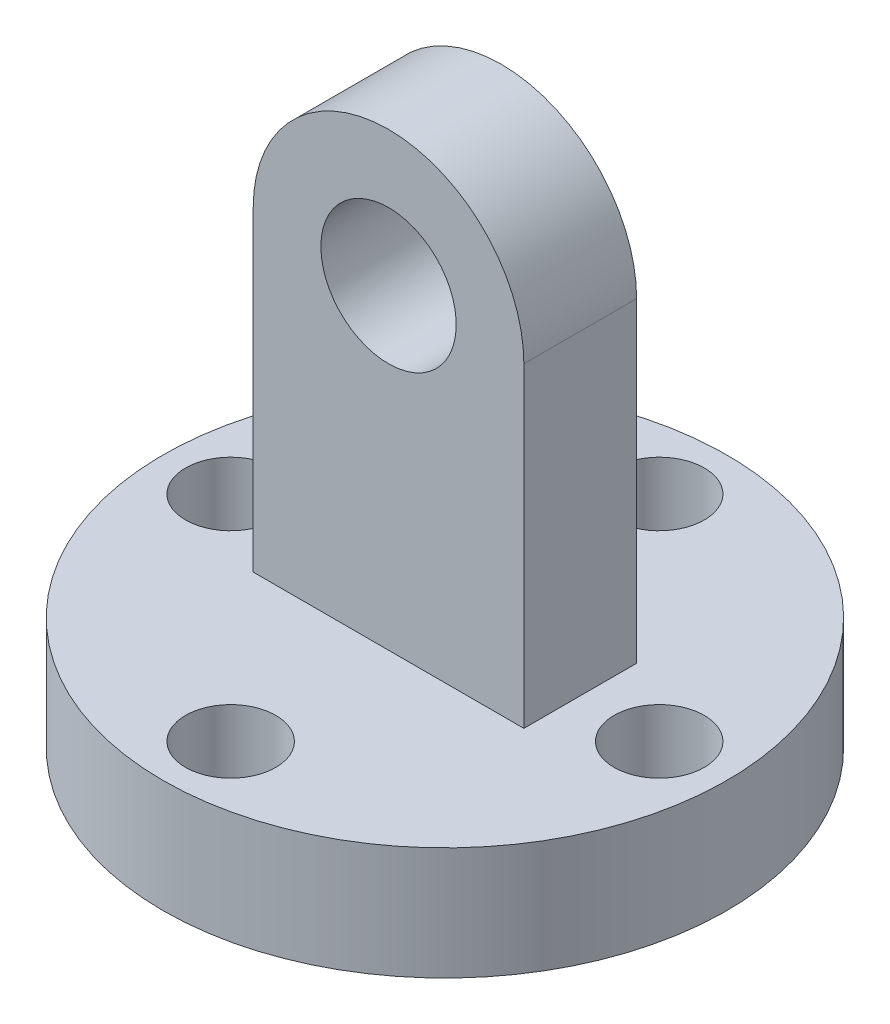
SolidWorks part; units mm, degrees
ref_plane "前视基准面" through (0, 0, 0) normal (0, 0, 1) x (1, 0, 0)
ref_plane "上视基准面" through (0, 0, 0) normal (0, 1, 0) x (1, 0, 0)
ref_plane "右视基准面" through (0, 0, 0) normal (1, 0, 0) x (0, 0, -1)
other "Configuration Table"
sketch "草图1" plane through (0, 0, 0) normal (0, 1, 0) x (1, 0, 0)
  circle A7 centre (0, 0) radius 12.5
  point P0 (0, 0)
  dimension "D4" = 25
extrude "凸台-拉伸1" add sketch "草图1" along normal blind 5
sketch "草图2" plane through (0, 5, 0) normal (0, 1, 0) x (1, 0, 0)
  line L0 (0, -9.5) -> (0, 9.5) construction
  line L1 (9.5, 0) -> (-9.5, 0) construction
  circle A0 centre (0, -9.5) radius 1.1
  circle A1 centre (0, 9.5) radius 1.1
  circle A2 centre (9.5, 0) radius 1.1
  circle A3 centre (-9.5, 0) radius 1.1
  circle A5 centre (-9.5, 0) radius 2
  circle A6 centre (0, 9.5) radius 2
  circle A7 centre (9.5, 0) radius 2
  circle A8 centre (0, -9.5) radius 2
  dimension "D1" = 2.2
  dimension "D3" = 4
  dimension "D2" = 19
extrude "切除-拉伸1" cut sketch "草图2" against normal through all contours A3 | A1 | A2 | A0
extrude "切除-拉伸2" cut sketch "草图2<3>" against normal offset from surface (3 mm away) 2 contours A5 | A6 | A8 | A7 up to face at (-9.5, 0, 1.1)
sketch "草图2<3>" plane through (0, 5, 0) normal (0, 1, 0) x (1, 0, 0) same geometry as "草图2"
sketch "草图3" plane through (0, 5, 0) normal (0, 1, 0) x (1, 0, 0)
  line L1 (6, 2.5) -> (-6, 2.5)
  line L2 (6, 2.5) -> (6, -2.5)
  line L3 (6, -2.5) -> (-6, -2.5)
  line L4 (-6, 2.5) -> (-6, -2.5)
  line L5 (6, 2.5) -> (-6, -2.5) construction
  line L6 (6, -2.5) -> (-6, 2.5) construction
  point P0 (0, 0)
  dimension "D1" = 12
  dimension "D2" = 5
extrude "凸台-拉伸2" add sketch "草图3" along normal blind 20
sketch "草图4" plane through (0, 0, -2.5) normal (0, 0, -1) x (-1, 0, 0)
  line L0 (6, 25) -> (6, 5) construction
  line L1 (-6, 25) -> (6, 25) construction
  line L2 (-6, 25) -> (-6, 5) construction
  circle A0 centre (0, 19) radius 6
  circle A1 centre (0, 19) radius 3
  line M2 (6, 5) -> (6, 25)
  line M3 (6, 25) -> (-6, 25)
  line M4 (-6, 25) -> (-6, 5)
  dimension "D1" = 3
extrude "切除-拉伸3" cut sketch "草图4" against normal through all contours A0 M2 M3 | A0 M3 M4 | A1 region at (-4.6598, 23.6598, -2.5) region at (4.6598, 23.6598, -2.5) region at (0, 19, -2.5)
